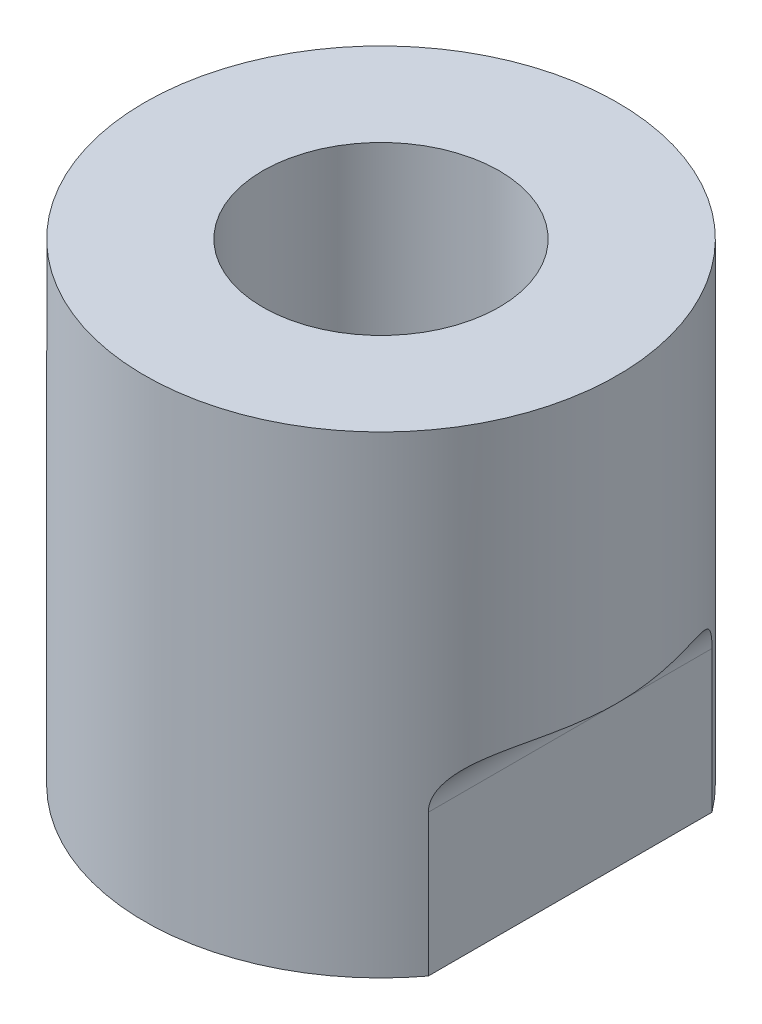
SolidWorks part; units mm, degrees
ref_plane "Plano frontal" through (0, 0, 0) normal (0, 0, 1) x (1, 0, 0)
ref_plane "Plano superior" through (0, 0, 0) normal (0, 1, 0) x (1, 0, 0)
ref_plane "Plano direito" through (0, 0, 0) normal (1, 0, 0) x (0, 0, -1)
sketch "Esboço1" plane through (0, 0, 0) normal (0, 0, 1) x (1, 0, 0)
  line L0 (0, 0) -> (-25, 0)
  line L2 (-25, 50) -> (-12.5, 50)
  line L3 (-12.5, 50) -> (-12.5, 10)
  line L4 (-12.5, 10) -> (0, 10)
  line L5 (0, 10) -> (0, 0)
  line L8 (-25, 50) -> (-25, 0)
  point P7 (-25, 48.1391)
  point P9 (-25, 50)
  point P10 (-25, 49.3012)
  dimension "D1" = 12.5
  dimension "D2" = 10
  dimension "D4" = 50
  dimension "D6" = 25
revolve "Revolução1" add sketch "Esboço1" angle 360 about L5
sketch "Esboço2" plane through (0, 10, 0) normal (0, 1, 0) x (1, 0, 0)
  line L0 (0, 7) -> (0, -7) construction
  circle A0 centre (0, 7) radius 6.25 construction
  circle A1 centre (0, -7) radius 6.25 construction
  circle A2 centre (0, 7) radius 4.9
  circle A3 centre (0, -7) radius 4.9
  circle A5 centre (0, 7) radius 5.5 construction
  circle A6 centre (0, 0) radius 12.5 construction
  point P6 (0, 0)
  dimension "D1" = 12.5
  dimension "D2" = 9.8
  dimension "D3" = 11
extrude "Corte-extrusão1" cut sketch "Esboço2" against normal up to surface (10 mm away) up to face at (-25, 0, 0)
chamfer "Chanfro1" distance 0.5 angle 45 2 edges at (4.9, 0, -7) (4.9, 0, 7)
sketch "Esboço3" plane through (0, 0, 0) normal (0, 0, 1) x (1, 0, 0)
  line L1 (-25, 0) -> (-20, 0)
  line L2 (-25, 0) -> (-25, 20)
  line L3 (-25, 20) -> (-20, 20)
  line L4 (-20, 0) -> (-20, 20)
  line L5 (25, 0) -> (20, 0)
  line L6 (25, 0) -> (25, 20)
  line L7 (25, 20) -> (20, 20)
  line L8 (20, 0) -> (20, 20)
  dimension "D1" = 5
  dimension "D2" = 20
extrude "Corte-extrusão2" cut sketch "Esboço3" against normal through all and the other way through all
fillet "Filete1" radius 5 2 edges at (20, 20, 0) (-20, 20, 0)
